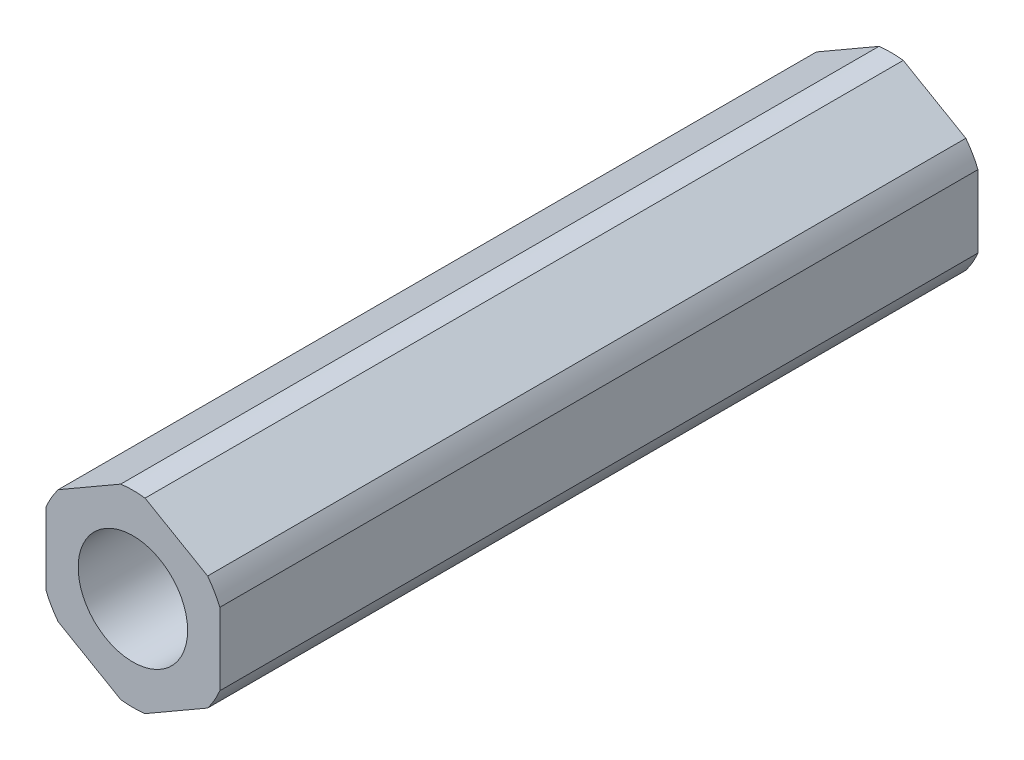
SolidWorks part; units mm, degrees
material "ThunderHex"
ref_plane "Front Plane" through (0, 0, 0) normal (0, 0, 1) x (1, 0, 0)
ref_plane "Top Plane" through (0, 0, 0) normal (0, 1, 0) x (1, 0, 0)
ref_plane "Right Plane" through (0, 0, 0) normal (1, 0, 0) x (0, 0, -1)
ref_plane "End1" through (0, 0, 27.7025) normal (0, 0, 1) x (1, 0, 0)
ref_plane "End2" through (0, 0, -27.7025) normal (0, 0, 1) x (1, 0, 0)
sketch "Sketch1" plane through (0, 0, 0) normal (0, 0, 1) x (1, 0, 0)
  circle A0 centre (0, 0) radius 6.35
  dimension "D1" = 12.7
extrude "Basic Rod" add sketch "Sketch1" along normal up to surface (27.7025 mm away) and the other way up to surface (27.7025 mm away) up to plane "End1" other way up to plane "End2"
ref_axis "Center Axis" through (0, 0, -38.2778) along (0, 0, 1)
sketch "Sketch8" plane through (0, 0, 0) normal (0, 0, 1) x (1, 0, 0)
  line L0 (-5.4616, 4.1791) -> (-6.35, 3.6662) construction
  line L1 (-0.8884, 6.8194) -> (-5.4616, 4.1791)
  line L2 (-6.35, 2.6403) -> (-6.35, -2.6403)
  line L3 (-5.4616, -4.1791) -> (-0.8884, -6.8194)
  line L4 (0.8884, -6.8194) -> (5.4616, -4.1791)
  line L5 (6.35, -2.6403) -> (6.35, 2.6403)
  line L6 (5.4616, 4.1791) -> (0.8884, 6.8194)
  line L7 (-6.35, 3.6662) -> (-6.35, 2.6403) construction
  line L8 (0, 7.3323) -> (-0.8884, 6.8194) construction
  line L9 (0.8884, 6.8194) -> (0, 7.3323) construction
  line L10 (6.35, 3.6662) -> (5.4616, 4.1791) construction
  line L11 (6.35, 2.6403) -> (6.35, 3.6662) construction
  line L12 (6.35, -3.6662) -> (6.35, -2.6403) construction
  line L13 (5.4616, -4.1791) -> (6.35, -3.6662) construction
  line L14 (0, -7.3323) -> (0.8884, -6.8194) construction
  line L15 (-0.8884, -6.8194) -> (0, -7.3323) construction
  line L16 (-6.35, -3.6662) -> (-5.4616, -4.1791) construction
  line L17 (-6.35, -2.6403) -> (-6.35, -3.6662) construction
  circle A0 centre (0, 0) radius 6.35 construction
  arc A1 (-6.35, -2.6403) -> (-5.4616, -4.1791) centre (0, 0) ccw
  circle A2 centre (0, 0) radius 6.35 construction
  arc A3 (-6.35, 2.6403) -> (-6.35, -2.6403) centre (0, 0) ccw construction
  arc A4 (-0.8884, 6.8194) -> (-5.4616, 4.1791) centre (0, 0) ccw construction
  arc A5 (-5.4616, 4.1791) -> (-6.35, 2.6403) centre (0, 0) ccw
  arc A6 (5.4616, 4.1791) -> (0.8884, 6.8194) centre (0, 0) ccw construction
  arc A7 (0.8884, 6.8194) -> (-0.8884, 6.8194) centre (0, 0) ccw
  arc A8 (6.35, -2.6403) -> (6.35, 2.6403) centre (0, 0) ccw construction
  arc A9 (6.35, 2.6403) -> (5.4616, 4.1791) centre (0, 0) ccw
  arc A10 (0.8884, -6.8194) -> (5.4616, -4.1791) centre (0, 0) ccw construction
  arc A11 (5.4616, -4.1791) -> (6.35, -2.6403) centre (0, 0) ccw
  arc A12 (-5.4616, -4.1791) -> (-0.8884, -6.8194) centre (0, 0) ccw construction
  arc A13 (-0.8884, -6.8194) -> (0.8884, -6.8194) centre (0, 0) ccw
  dimension "D1" = 13.7541
extrude "THex" add sketch "Sketch8" along normal mid plane 55.405
sketch "Sketch5" plane through (0, 0, 0) normal (0, 0, 1) x (1, 0, 0)
  line L1 (-3.6662, 6.35) -> (-7.3323, 0)
  line L2 (-7.3323, 0) -> (-3.6662, -6.35)
  line L3 (-3.6662, -6.35) -> (3.6662, -6.35)
  line L4 (3.6662, -6.35) -> (7.3323, 0)
  line L5 (7.3323, 0) -> (3.6662, 6.35)
  line L6 (3.6662, 6.35) -> (-3.6662, 6.35)
  circle A0 centre (0, 0) radius 6.35 construction
  circle A2 centre (0, 0) radius 6.35 construction
extrude "Hex" [suppressed] add sketch "Sketch5" along normal mid plane 55.405
sketch "Sketch7" plane through (0, 0, 0) normal (1, 0, 0) x (0, 0, -1)
  line L0 (0, 0) -> (-50000, 0) construction
  line L1 (-27.7025, 5.9436) -> (-28.7185, 5.9436)
  line L2 (-28.7185, 5.9436) -> (-28.7185, 6.35)
  line L3 (-28.7185, 6.35) -> (-29.7345, 6.35)
  line L4 (-30.2425, 5.842) -> (-30.2425, 0)
  line L5 (-30.2425, 0) -> (-27.7025, 0)
  line L6 (-27.7025, 0) -> (-27.7025, 5.9436)
  line L7 (-29.7345, 6.35) -> (-30.2425, 5.842)
  line L8 (38.2778, 0) -> (-38.2778, 0) construction
  line L9 (-27.7025, 5.2388) -> (-27.7025, -5.2388) construction
  point P7 (-30.2425, 6.35)
  dimension "D1" = 12.7
  dimension "D4" = 1.016
  dimension "D2" = 0.4064
  dimension "D3" = 2.54
revolve "1stSnapRing" [suppressed] add sketch "Sketch7" angle 360 about axis through (0, 0, -38.2778) along (0, 0, 1)
mirror "2ndSnapRing" [suppressed] about plane through (0, 0, 0) normal (0, 0, 1)
sketch "Sketch2" plane through (0, 0, 0) normal (0, 0, 1) x (1, 0, 0)
  circle A0 centre (0, 0) radius 4
  dimension "D1" = 8
extrude "Internal Cut" cut sketch "Sketch2" against normal through all both and the other way through all
equation "\"Unit Measure\"= \"Length\"'in"
equation "\"D1@Sketch1\"=\"OD\""
equation "\"D1\"= \"Length\""
equation "\"Internal Cut\"= IIF ( \"ID\" = 0 ,  suppressed  ,  unsuppressed  ) "
equation "\"D1@Hex\" = \"Length\""
equation "\"Hex\" = IIF ( \"SelectionType\" = 1 , \"suppressed\" , iif ( \"SelectionType\" = 2 , \"suppressed\" , \"unsuppressed\" ) )"
equation "\"OutsideDiameter\"= \"OD\"'in"
equation "\"ThunderHexDia\"= iif ( \"OD\" < .36 , \"OD\" * 1.1 , iif ( \"OD\" < .40 , .4035 , iif ( \"OD\" < .52 , .5415 , \"OD\" * 1.1 ) ) )"
equation "\"D1@Sketch7\"=\"Thickness\""
equation "\"SRDia\"= iif ( \"OD\" = .5 , ( \"OD\" - .468 ) / 2 , iif ( \"OD\" = .375 , ( \"OD\" - .352 ) / 2 , .050 ) )"
equation "\"D2@Sketch7\"= \"SnapRingDepth\""
equation "\"1stSnapRing\"= iif ( \"SnapRingCount\" > 0 , \"unsuppressed\" , \"suppressed\" )"
equation "\"2ndSnapRing\"= iif ( \"SnapRingCount\" = 2 , \"unsuppressed\" , \"suppressed\" )"
equation "\"D1@End1\" = \"Length\" / 2"
equation "\"D1@End2\" = \"Length\""
equation "\"D1@Sketch8\"=\"ThunderHexDia\""
equation "\"D1@THex\" = \"Length\""
equation "\"THex\"= IIF ( \"SelectionType\" = 0 ,  suppressed  , iif ( \"SelectionType\" = 2 ,  suppressed  ,  unsuppressed  )  ) "
